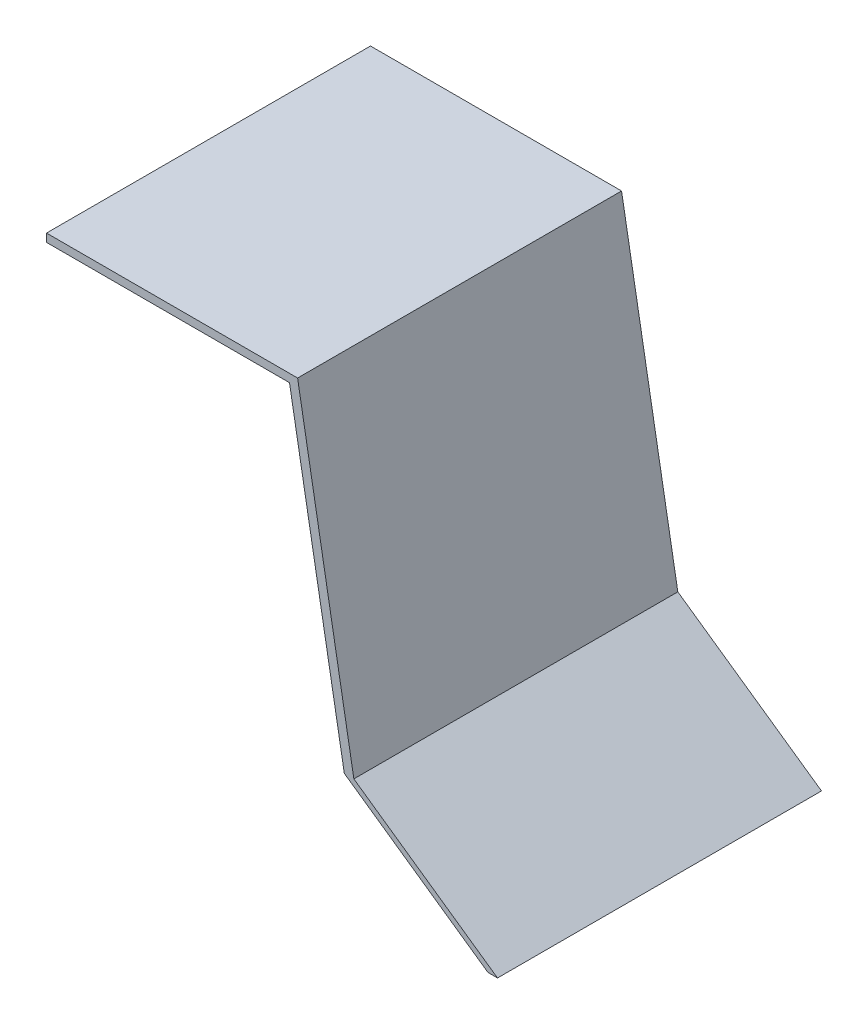
SolidWorks part; units mm, degrees
ref_plane "Front Plane" through (0, 0, 0) normal (0, 0, 1) x (1, 0, 0)
ref_plane "Top Plane" through (0, 0, 0) normal (0, 1, 0) x (1, 0, 0)
ref_plane "Right Plane" through (0, 0, 0) normal (1, 0, 0) x (0, 0, -1)
sketch "Sketch1" plane through (0, 0, 0) normal (0, 1, 0) x (1, 0, 0)
  line L1 (127, 0) -> (508, 0)
  line L2 (127, 0) -> (127, 508)
  line L3 (127, 508) -> (508, 508)
  line L4 (508, 0) -> (508, 508)
  dimension "D1" = 508
  dimension "D2" = 508
  dimension "D3" = 127
extrude "Boss-Extrude1" add sketch "Sketch1" along normal blind 12.7 contours L2 L3 L4 L1
ref_plane "Plane1" through (317.5, 0, 0) normal (1, 0, 0) x (0, 0, -1)
sketch "Sketch3" plane through (317.5, 0, 0) normal (1, 0, 0) x (0, 0, -1)
  line L0 (234.95, 0) -> (234.95, -50.8)
  line L1 (0, 0) -> (508, 0) construction
  line L4 (273.05, -50.8) -> (273.05, -34.925)
  line L5 (273.05, -34.925) -> (260.35, -34.925)
  line L6 (260.35, -34.925) -> (260.35, -50.8)
  line L8 (234.95, 0) -> (247.65, 0)
  line L9 (247.65, 0) -> (247.65, -50.8)
  line L10 (254, 0) -> (254, -69.85) construction
  arc A0 (234.95, -50.8) -> (273.05, -50.8) centre (254, -50.8) ccw
  arc A3 (260.35, -50.8) -> (247.65, -50.8) centre (254, -50.8) cw
  point P6 (254, -69.85)
  point P12 (254, -34.925)
  point P14 (266.7, -34.925)
  point P15 (0, 0)
  point P16 (254, -57.15)
  point P19 (254, 0)
  dimension "D3" = 50.8
  dimension "D4" = 12.7
  dimension "D1" = 6.35
  dimension "D2" = 12.7
extrude "Boss-Extrude2" add sketch "Sketch3" along normal mid plane 25.4
sketch "Sketch6" plane through (0, 0, 0) normal (0, 0, 1) x (1, 0, 0)
  line L0 (520.7, 12.7) -> (608.9133, -487.5823)
  line L2 (593.9739, -487.5823) -> (508, 0)
  line L4 (127, 0) -> (508, 0) construction
  line L5 (508, 0) -> (508, 12.7)
  line L6 (508, 12.7) -> (520.7, 12.7)
  line L7 (608.9133, -487.5823) -> (834.1808, -645.3163)
  line L8 (834.1808, -645.3163) -> (819.2414, -645.3163)
  line L9 (819.2414, -645.3163) -> (593.9739, -487.5823)
  dimension "D1" = 508
  dimension "D2" = 100
  dimension "D3" = 12.7
  dimension "D4" = 35
  dimension "D5" = 157.734
extrude "Boss-Extrude4" add sketch "Sketch6" against normal up to surface (508 mm away) up to face at (317.5, 6.35, -508)
